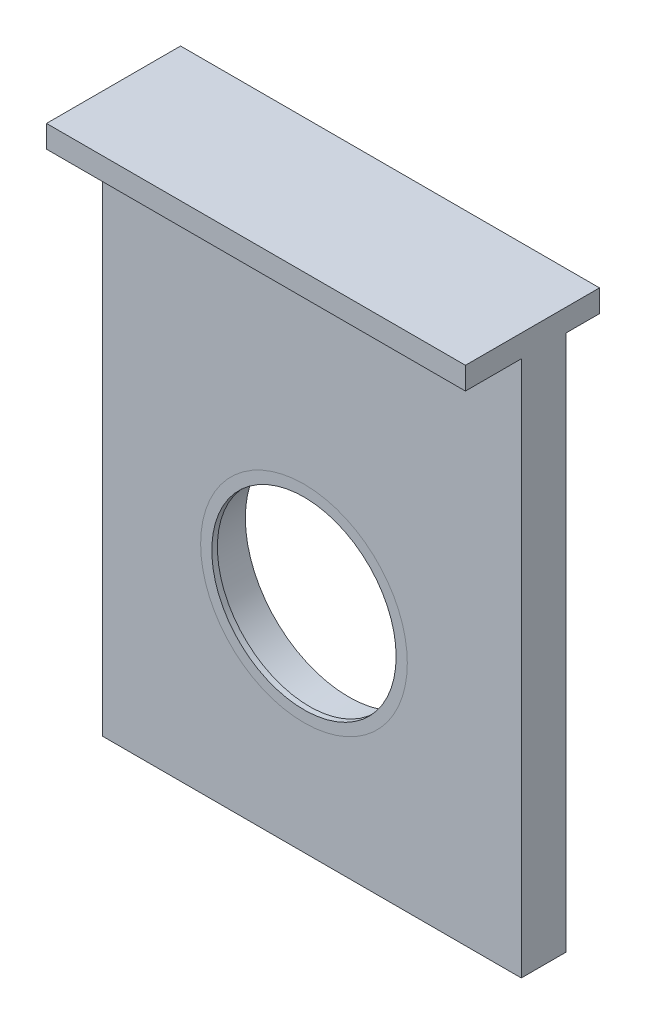
SolidWorks part; units mm, degrees
ref_plane "Front Plane" through (0, 0, 0) normal (0, 0, 1) x (1, 0, 0)
ref_plane "Top Plane" through (0, 0, 0) normal (0, 1, 0) x (1, 0, 0)
ref_plane "Right Plane" through (0, 0, 0) normal (1, 0, 0) x (0, 0, -1)
sketch "Sketch12" plane through (0, 0, 0) normal (0, 0, 1) x (1, 0, 0)
  line L0 (62.1258, 0) -> (62.1258, 100)
  line L1 (62.1258, 100) -> (137.1258, 100)
  line L2 (62.1258, 0) -> (137.1258, 0)
  line L3 (137.1258, 100) -> (137.1258, 0)
  circle A0 centre (99.6258, 37.5) radius 25.4
  circle A1 centre (99.6258, 37.5) radius 6.5
  dimension "D3" = 50.8
  dimension "D4" = 13
  dimension "D1" = 100
  dimension "D2" = 75
extrude "Boss-Extrude10" add sketch "Sketch12" along normal blind 8 separate body contours L1 L3 L2 L0
sketch "Sketch15" plane through (0, 0, 8) normal (0, 0, 1) x (1, 0, 0)
  circle A0 centre (98.2196, 38.6276) radius 25.4
  dimension "D1" = 50.8
sketch "Sketch24" plane through (0, 0, 8) normal (0, 0, 1) x (1, 0, 0)
  line L0 (62.1258, 100) -> (62.1258, 96)
  line L1 (62.1258, 0) -> (62.1258, 100) construction
  line L2 (62.1258, 96) -> (137.1258, 96)
  line L3 (137.1258, 100) -> (137.1258, 0) construction
  line L4 (137.1258, 96) -> (137.1258, 100)
  line L5 (137.1258, 100) -> (62.1258, 100)
  dimension "D1" = 4
extrude "Boss-Extrude13" add sketch "Sketch24" along normal blind 10 and the other way blind 14
sketch "Sketch25" plane through (0, 0, 8) normal (0, 0, 1) x (1, 0, 0)
  circle A0 centre (98.2196, 38.6276) radius 18.5
  dimension "D1" = 37
extrude "Cut-Extrude1" cut sketch "Sketch25" against normal through all
sketch "Sketch26" plane through (0, 0, 8) normal (0, 0, 1) x (1, 0, 0)
  circle A0 centre (98.2196, 38.6276) radius 16.5
  circle A1 centre (98.2196, 38.6276) radius 18.5
  dimension "D1" = 37
  dimension "D2" = 2
extrude "Boss-Extrude15" add sketch "Sketch26" against normal blind 1 separate body
